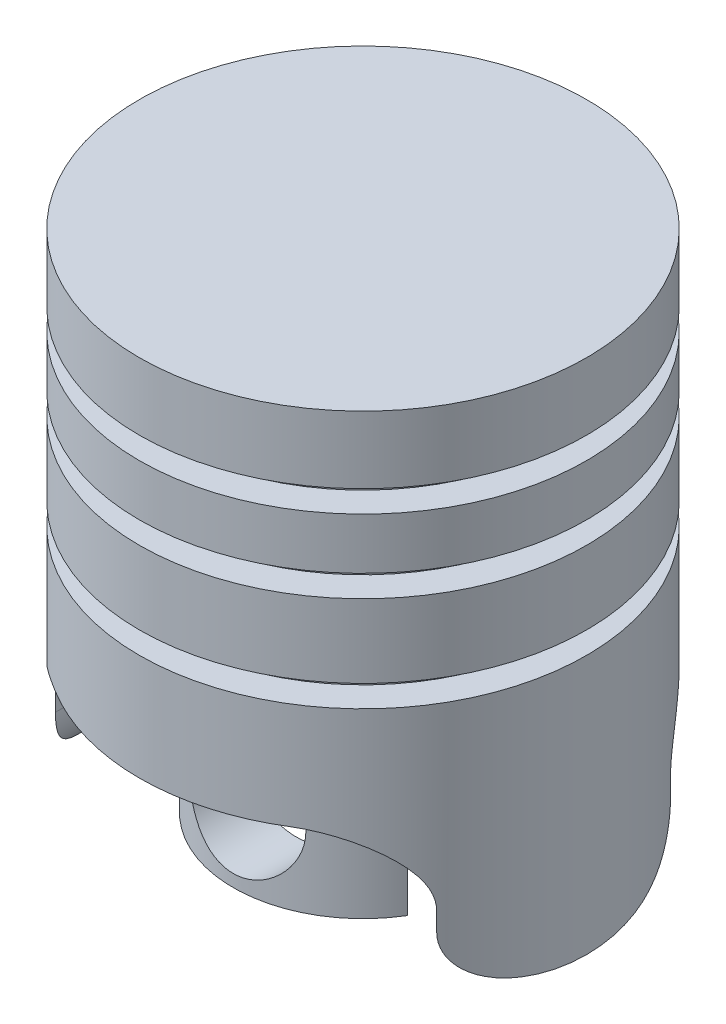
SolidWorks part; units mm, degrees
ref_plane "Front Plane" through (0, 0, 0) normal (0, 0, 1) x (1, 0, 0)
ref_plane "Top Plane" through (0, 0, 0) normal (0, 1, 0) x (1, 0, 0)
ref_plane "Right Plane" through (0, 0, 0) normal (1, 0, 0) x (0, 0, -1)
sketch "Sketch1" plane through (0, 0, 0) normal (0, 0, 1) x (1, 0, 0)
  line L0 (0, 35.0964) -> (0, -39.7586) construction
  line L1 (0, 27.326) -> (-30.5, 27.326)
  line L2 (-30.5, 27.326) -> (-30.5, 18.166)
  line L3 (-30.5, 18.166) -> (-26.5, 18.166)
  line L4 (-26.5, 18.166) -> (-26.5, 15.166)
  line L5 (-26.5, 15.166) -> (-30.5, 15.166)
  line L6 (-30.5, 15.166) -> (-30.5, 8.166)
  line L7 (-30.5, 8.166) -> (-26.5, 8.166)
  line L8 (-26.5, 8.166) -> (-26.5, 5.166)
  line L9 (-26.5, 5.166) -> (-30.5, 5.166)
  line L10 (-30.5, 5.166) -> (-30.5, -4.834)
  line L11 (-30.5, -4.834) -> (-26.5, -4.834)
  line L12 (-26.5, -4.834) -> (-26.5, -7.834)
  line L13 (-26.5, -7.834) -> (-30.5, -7.834)
  line L14 (-30.5, -7.834) -> (-30.5, -44.834)
  line L15 (-30.5, -44.834) -> (-17.7, -44.834)
  line L16 (-17.7, -44.834) -> (-17.7, 14.326)
  line L17 (-17.7, 14.326) -> (0, 14.326)
  line L18 (0, 14.326) -> (0, 27.326)
  dimension "D1" = 30.5
  dimension "D2" = 13
  dimension "D3" = 59.16
  dimension "D4" = 37
  dimension "D5" = 10
  dimension "D6" = 3
  dimension "D7" = 4
  dimension "D9" = 7
  dimension "D10" = 12.8
revolve "Revolve1" add sketch "Sketch1" angle 360 about L0
sketch "Sketch2" plane through (0, 0, 0) normal (0, 0, 1) x (1, 0, 0)
  line L0 (-30.5, -44.834) -> (30.5, -44.834) construction
  line L1 (-26, -67.334) -> (26, -67.334)
  line L2 (-26, -67.334) -> (-26, -22.334)
  line L3 (-26, -22.334) -> (26, -22.334)
  line L4 (26, -67.334) -> (26, -22.334)
  line L5 (-26, -67.334) -> (26, -22.334) construction
  line L6 (-26, -22.334) -> (26, -67.334) construction
  point P0 (0, -44.834)
  dimension "D1" = 52
  dimension "D2" = 45
extrude "Cut-Extrude1" cut sketch "Sketch2" against normal through all both and the other way through all
fillet "Fillet1" radius 10 2 edges at (-26, -22.334, 0) (26, -22.334, 0)
sketch "Sketch3" plane through (0, 14.326, 0) normal (0, -1, 0) x (1, 0, 0)
  line L1 (-15.1861, -9.0925) -> (15.1861, -9.0925)
  line L2 (-15.1861, 9.0925) -> (15.1861, 9.0925)
  circle A1 centre (0, 0) radius 17.7
  circle A2 centre (0, 0) radius 17.7
  circle M3 centre (0, 0) radius 17.7
  dimension "D1" = 0
extrude "Boss-Extrude1" add sketch "Sketch3" along normal blind 56 contours L2 M3 | L1 M3
sketch "Sketch4" plane through (0, 0, 0) normal (0, 0, 1) x (1, 0, 0)
  circle A0 centre (0, -32) radius 8
  dimension "D1" = 16
  dimension "D2" = 32
extrude "Cut-Extrude2" cut sketch "Sketch4" against normal through all both and the other way through all
fillet "Fillet2" radius 10 2 edges at (26, -44.834, 0) (-26, -44.834, 0)
